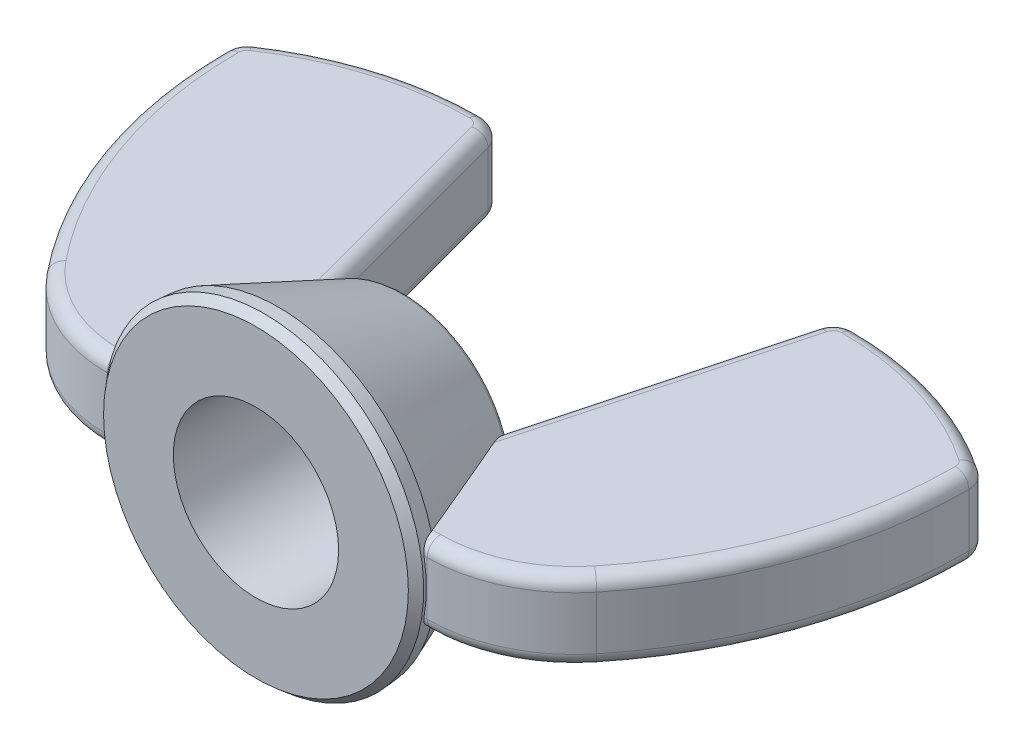
SolidWorks part; units mm, degrees
material "AISI 304"
ref_plane "Front Plane" through (0, 0, 0) normal (0, 0, 1) x (1, 0, 0)
ref_plane "Top Plane" through (0, 0, 0) normal (0, 1, 0) x (1, 0, 0)
ref_plane "Right Plane" through (0, 0, 0) normal (1, 0, 0) x (0, 0, -1)
sketch "Sketch1" plane through (0, 0, 0) normal (0, 0, 1) x (1, 0, 0)
  circle A0 centre (0, 0) radius 3.175
  circle A1 centre (0, 0) radius 6.1516
  dimension "D1" = 12.3031
sketch "Sketch2" plane through (0, 0, 0) normal (0, 1, 0) x (1, 0, 0)
  line L0 (0, 0) -> (0, 15.875) construction
  line L1 (-3.175, 0) -> (3.175, 0) construction
  line L2 (-14.2875, 15.875) -> (14.2875, 15.875) construction
  line L3 (14.2875, 15.875) -> (14.2875, 0) construction
  line L4 (-14.2875, 15.875) -> (-14.2875, 0) construction
  line L5 (-14.2875, 0) -> (14.2875, 0) construction
  line L6 (-4.1928, 5.715) -> (4.1928, 5.715) construction
  line L7 (0, 0) -> (0, 5.715) construction
  line L8 (-4.3144, 0.8572) -> (6.1516, 0.8572) construction
  line L9 (6.1516, 0) -> (6.1516, 5.715) construction
  line L10 (3.7735, 5.715) -> (6.5552, 16.0963)
  line L12 (4.1928, 5.715) -> (4.1928, 0.4286) construction
  line L13 (-6.1516, 0) -> (6.1516, 0) construction
  line L14 (6.1516, 0.8572) -> (4.1928, 5.715) construction
  line L15 (6.5552, 16.0963) -> (14.6189, 13.631)
  line L16 (14.6189, 13.631) -> (8.5296, 0.4286)
  line L17 (6.1516, 0.4286) -> (8.5296, 0.4286)
  line L19 (3.7735, 0.4286) -> (6.1516, 0.4286)
  line L20 (-3.7735, 5.715) -> (3.7735, 5.715) construction
  line L21 (3.7735, 5.715) -> (3.7735, 0.4286)
  circle A3 centre (13.4331, 13.1001) radius 0.8544 construction
  circle A4 centre (7.1515, 15.0206) radius 0.8544 construction
  dimension "D6" = 1.7088
  dimension "D2" = 5.715
  dimension "D4" = 8.3857
  dimension "D1" = 0.8572
  dimension "D3" = 21.96
  dimension "D5" = 0.4286
  dimension "D8" = 17
  dimension "D9" = 7.5471
  dimension "D7" = 15
sketch "Sketch13" plane through (0, 0, 0) normal (0, 1, 0) x (1, 0, 0)
  line L1 (3.7735, 5.715) -> (3.7735, 0.4286) construction
  line L2 (3.7735, 5.715) -> (6.5552, 16.0963) construction
  line L3 (-14.2875, 15.875) -> (14.2875, 15.875) construction
  line L4 (14.2875, 15.875) -> (14.2875, 0) construction
  line L5 (6.1516, 0.4286) -> (8.5296, 0.4286) construction
  line L6 (3.7735, 0.4286) -> (6.1516, 0.4286) construction
  line L7 (0, 0) -> (0, 5.715) construction
  line L8 (-3.175, 0) -> (3.175, 0) construction
  line L9 (0, 0) -> (0, 15.875) construction
  line L10 (-4.1928, 5.715) -> (4.1928, 5.715) construction
  line L11 (3.7735, 0.4286) -> (6.1516, 0.4286)
  line L12 (3.7735, 5.715) -> (3.7735, 0.4286)
  line L13 (3.7735, 5.715) -> (6.3262, 15.2417)
  circle A0 centre (13.4331, 13.1001) radius 0.8544 construction
  circle A1 centre (7.1515, 15.0206) radius 0.8544 construction
  arc A5 (14.2875, 13.1001) -> (13.9109, 13.8084) centre (13.4331, 13.1001) ccw
  arc A6 (7.1515, 15.875) -> (6.3262, 15.2417) centre (7.1515, 15.0206) ccw
  arc A7 (10.5535, 2.5321) -> (14.2875, 13.1001) centre (-2.5346, 13.1001) ccw
  arc A8 (13.9109, 13.8084) -> (7.1515, 15.875) centre (7.1515, 3.7873) ccw
  arc A10 (6.1516, 0.4286) -> (10.5535, 2.5321) centre (6.1516, 6.0864) ccw
extrude "Extrude2" add sketch "Sketch13" along normal mid plane 3.0758
sketch "Sketch3" plane through (0, 0, 0) normal (0, 0, 1) x (1, 0, 0)
  circle A0 centre (0, 0) radius 6.1516 construction
  circle A1 centre (0, 0) radius 6.1516
extrude "Extrude1" add sketch "Sketch3" against normal up to vertex (0.8572 mm away) draft 5 separate body up to point (6.1516, 0, -0.8572)
sketch "Sketch15" plane through (0, 0, -0.8572) normal (0, 0, -1) x (-1, 0, 0)
  circle A1 centre (0, 0) radius 6.0766
  circle A2 centre (0, 0) radius 6.0766
  dimension "D1" = 0
extrude "Extrude3" add sketch "Sketch15" along normal up to vertex (4.8578 mm away) draft 21.96 up to point (0, 0, -5.715)
fillet "Fillet3" radius 0.254 1 edges at (-4.1178, 0, -5.715)
sketch "Sketch12" plane through (0, 0, -5.715) normal (0, 0, -1) x (-1, 0, 0)
  circle A1 centre (0, 0) radius 6.0766
  circle A2 centre (0, 0) radius 6.0766 construction
  dimension "D1" = 12.1531
sketch "Sketch4" plane through (0, 0, 0) normal (0, 0, 1) x (1, 0, 0)
  circle A0 centre (0, 0) radius 3.175 construction
  circle A1 centre (0, 0) radius 3.175
extrude "Cut-Extrude1" cut sketch "Sketch4" against normal through all
sketch "Sketch5" plane through (0, 0, 0) normal (0, 0, 1) x (1, 0, 0)
  circle A0 centre (0, 0) radius 3.175 construction
  circle A1 centre (0, 0) radius 3.175
curve "Helix/Spiral1" pitch 1.27 height 8.89 turns 7 parameters "pitch"=1.27
sketch "Sketch6" plane through (0, 0, 0) normal (0, 1, 0) x (1, 0, 0)
  line L0 (-3.175, -1.1112) -> (-2.3501, -0.635)
  line L1 (-2.3501, -0.635) -> (-2.3501, -0.4762)
  line L2 (-2.3501, -0.4762) -> (-3.175, 0)
  line L3 (-3.175, -1.1112) -> (-3.175, 0)
  line L4 (-3.175, -0.5556) -> (-2.3501, -0.5556) construction
  line L5 (-2.7626, -0.8731) -> (-2.7626, -0.2381) construction
  line L6 (-3.175, 0) -> (3.175, 0) construction
  dimension "D1" = 60
  dimension "D2" = 0.1588
  dimension "D3" = 0.635
sweep "Sweep1" [suppressed] add profiles "Sketch6" path "Helix/Spiral1"
sketch "Sketch7" plane through (0, 0, 0) normal (0, 0, 1) x (1, 0, 0)
  circle A1 centre (0, 0) radius 6.1516
  circle A2 centre (0, 0) radius 6.1516
  dimension "D1" = 0
extrude "Cut-Extrude2" [suppressed] cut sketch "Sketch7" along normal through all
ref_plane "Plane1" through (0, 0, -5.715) normal (0, 0, 1) x (1, 0, 0)
sketch "Sketch8" plane through (0, 0, -5.715) normal (0, 0, 1) x (1, 0, 0)
  circle A0 centre (0, 0) radius 6.0766 construction
  circle A2 centre (0, 0) radius 6.0766
extrude "Cut-Extrude3" [suppressed] cut sketch "Sketch8" against normal through all
sketch "Sketch9" plane through (0, 0, 0) normal (0, 0, 1) x (1, 0, 0)
  circle A1 centre (0, 0) radius 3.175
  circle A2 centre (0, 0) radius 3.175
  dimension "D1" = 0
extrude "Cut-Extrude4" [suppressed] cut sketch "Sketch9" against normal through all draft 45
sketch "Sketch11" plane through (0, 0, -5.715) normal (0, 0, 1) x (1, 0, 0)
  circle A0 centre (0, 0) radius 3.175 construction
  circle A1 centre (0, 0) radius 3.1242
  circle A2 centre (0, 0) radius 3.175 construction
  dimension "D1" = 0.0508
extrude "Cut-Extrude5" [suppressed] cut sketch "Sketch11" along normal through all draft 45
chamfer "Chamfer1" distance 0.3215 angle 45 1 edges at (6.1516, 0, 0) first distance on face at (-6.0766, 0, -0.8572)
fillet "Fillet4" radius 0.5126 14 edges at (4.9626, 1.5379, -0.4286) (8.5909, 1.5379, -0.9815) (6.6314, 1.5379, -15.6984) (10.6856, 1.5379, -15.3468) (14.1875, 1.5379, -13.5012) (4.9626, -1.5379, -0.4286) (8.5909, -1.5379, -0.9815) (6.6314, -1.5379, -15.6984) (10.6856, -1.5379, -15.3468) (14.1875, -1.5379, -13.5012) (13.3266, 1.5379, -7.496) (13.3266, -1.5379, -7.496) (5.0499, 1.5379, -10.4784) (5.0499, -1.5379, -10.4784)
mirror "Mirror6" about plane through (0, 0, 0) normal (1, 0, 0) of bodies 108 113
combine bodies "Combine2" operation type add bodies to combine 116 108 102
equation "\"D1@Sketch1\" = \"thread dia@Sketch1\"*1.725"
equation "\"D2@Sketch2\" = \"B@Sketch2\"*.36"
equation "\"D3@Helix/Spiral1\" = \"D2@Sketch2\"+.125"
equation "\"D2@Sketch6\" = \"pitch@Helix/Spiral1\"*.125"
equation "\"D3@Sketch6\" = \"pitch@Helix/Spiral1\"*.5"
equation "\"D4@Sketch2\" = \"D1@Sketch12\"*.69"
equation "\"D1@Extrude2\" = \"D1@Sketch1\"*.25"
equation "\"D1@Sketch2\" = \"D2@Sketch2\"*.150"
equation "\"D5@Sketch2\" = \"D1@Sketch2\"/2"
equation "\"D3@Extrude3\" = \"D3@Sketch2\""
equation "\"D1@Chamfer1\" = \"D5@Sketch2\"*.75"
equation "\"D9@Sketch2\" = \"D4@Sketch2\"*.9"
equation "\"D6@Sketch2\" = \"D1@Extrude2\"/1.8"
equation "\"D1@Fillet4\" = \"D1@Extrude2\"/6"
